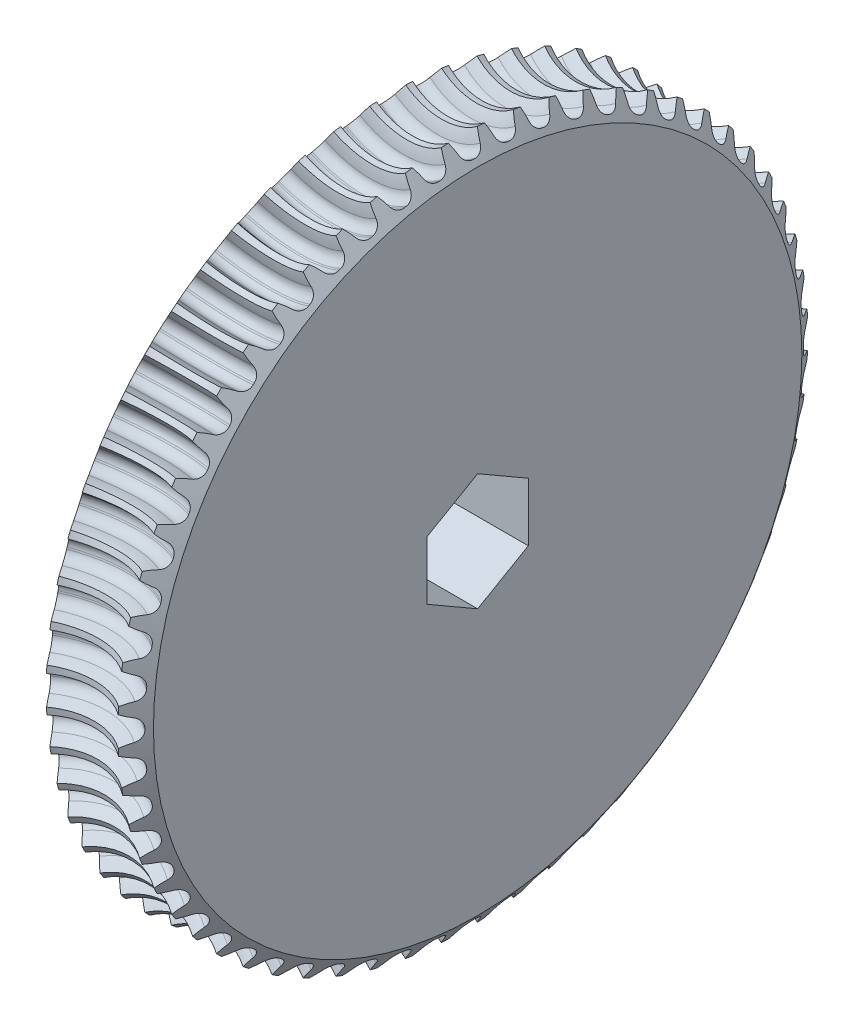
SolidWorks part; units mm, degrees
ref_plane "Piano frontale" through (0, 0, 0) normal (0, 0, 1) x (1, 0, 0)
ref_plane "Piano superiore" through (0, 0, 0) normal (0, 1, 0) x (1, 0, 0)
ref_plane "Piano destro" through (0, 0, 0) normal (1, 0, 0) x (0, 0, -1)
sketch "Schizzo1" plane through (0, 0, 0) normal (0, 0, 1) x (1, 0, 0)
  line L0 (-2.5, 0) -> (2.5, 0)
  line L1 (2.5, 0) -> (2.5, 16)
  line L3 (-2.5, 16) -> (-2.5, 0)
  line L4 (0.0015, 15.9453) -> (0.0015, 16.4453) construction
  line L5 (1.77, 17.022) -> (2.5, 16)
  line L6 (-1.769, 17.0235) -> (-2.5, 16)
  arc A0 (2.0606, 16.6151) -> (-2.0596, 16.6166) centre (0.0015, 19.4453) ccw construction
  arc A1 (-1.769, 17.0235) -> (1.77, 17.022) centre (0.0015, 19.4453) ccw
  dimension "D1" = 7
  dimension "D5" = 0.5
  dimension "D6" = 16
  dimension "D2" = 5
  dimension "D3" = 2.5
  dimension "D4" = 5
revolve "Rivoluzione1" add sketch "Schizzo1" angle 360 mid plane about L0
sketch "Schizzo2" plane through (0, 0, 0) normal (1, 0, 0) x (0, 0, -1)
  line L0 (0, 19.4453) -> (25.188, 19.4453) construction
  line L1 (0, 0) -> (0.5758, 16.4899) construction
  line L2 (0, 16) -> (0, 0) construction
  line L3 (0, 0) -> (0, 16.5) construction
  line L4 (0.5584, 15.9903) -> (4.3663, 14.8723) construction
  line L5 (1.5307, 17.6489) -> (-1.5307, 17.6489)
  line L6 (-0.4466, 15.4936) -> (0.4466, 15.4936)
  circle A0 centre (0, 0) radius 16
  circle A1 centre (0, 0) radius 16.5
  circle A2 centre (0, 0) radius 15.5
  arc A4 (-1.5307, 17.6489) -> (-0.4466, 15.4936) centre (-4.3663, 14.8723) cw
  arc A5 (1.5307, 17.6489) -> (0.4466, 15.4936) centre (4.3663, 14.8723) ccw
  dimension "D1" = 32
  dimension "D4" = 2
  dimension "D2" = 0.5
  dimension "D3" = 0.5
revolve "Taglia-Rivoluzione1" cut sketch "Schizzo2" angle 360 about L0
fillet "Raccordo2" radius 0.5 2 edges at (0, 15.4936, -0.4466) (0, 15.4936, 0.4466)
pattern_circular "RipetizioneCircolare1" count 60 every 6 about axis through (1.77, 0, 0) along (-1, 0, 0) of "Raccordo2", "Taglia-Rivoluzione1"
sketch "Schizzo3" plane through (0, 0, 0) normal (1, 0, 0) x (0, 0, -1)
  line L1 (0, 2.8868) -> (-2.5, 1.4434)
  line L2 (-2.5, 1.4434) -> (-2.5, -1.4434)
  line L3 (-2.5, -1.4434) -> (0, -2.8868)
  line L4 (0, -2.8868) -> (2.5, -1.4434)
  line L5 (2.5, -1.4434) -> (2.5, 1.4434)
  line L6 (2.5, 1.4434) -> (0, 2.8868)
  circle A0 centre (0, 0) radius 2.5 construction
  dimension "D1" = 2.5
extrude "Taglio-Estrusione1" cut sketch "Schizzo3" against normal through all both and the other way through all
sketch "Schizzo4" plane through (0, 0, 0) normal (1, 0, 0) x (0, 0, -1)
  circle A0 centre (0, 0) radius 16
